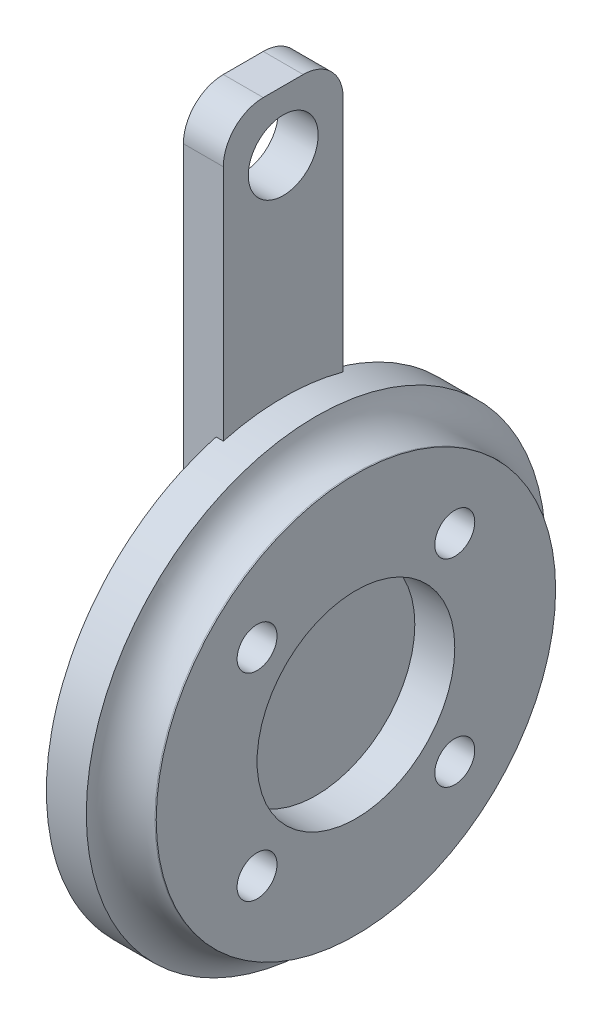
SolidWorks part; units mm, degrees
material "PLA"
ref_plane "Front Plane" through (0, 0, 0) normal (1, 0, 0) x (0, 1, 0)
ref_plane "Top Plane" through (0, 0, 0) normal (0, 0, 1) x (0, 1, 0)
ref_plane "Right Plane" through (0, 0, 0) normal (0, 1, 0) x (-1, 0, 0)
sketch "Sketch1" plane through (0, 0, 0) normal (1, 0, 0) x (0, 1, 0)
  circle A0 centre (0, 0) radius 11.5
  circle A1 centre (0, 0) radius 10.5
  dimension "D1" = 1
  dimension "D2" = 21
extrude "Boss-Extrude1" add sketch "Sketch1" along normal blind 2
extrude "Boss-Extrude2" add sketch "Sketch1<2>" along normal up to surface (2 mm away) contours A1 region at (0, 0, 0) up to face at (2, 0, -11.5)
sketch "Sketch1<2>" plane through (0, 0, 0) normal (1, 0, 0) x (0, 1, 0) same geometry as "Sketch1"
ref_plane "Plane1" through (-1.64, 0, 0) normal (-1, 0, 0) x (0, 0, 1)
sketch "Sketch2" plane through (-1.64, 0, 0) normal (-1, 0, 0) x (0, 0, 1)
  line L1 (-3, -5) -> (3, -5)
  line L2 (-3, -5) -> (-3, 5)
  line L3 (-3, 5) -> (3, 5)
  line L4 (3, -5) -> (3, 5)
  line L5 (0, 5) -> (0, -5) construction
  line L6 (-3, 0) -> (3, 0) construction
  point P0 (0, 0)
  dimension "D1" = 6
  dimension "D2" = 10
sketch "Sketch3" plane through (0, 0, 0) normal (-1, 0, 0) x (0, -1, 0)
  circle A0 centre (0, 0) radius 11.5
  circle A1 centre (0, 0) radius 9.5
  circle A2 centre (0, 0) radius 11.5 construction
  dimension "D1" = 2
extrude "Cut-Extrude2" cut sketch "Sketch3" against normal blind 1.5 contours A1 region at (0, 0, 0)
sketch "Sketch4" plane through (0, 0, 0) normal (-1, 0, 0) x (0, -1, 0)
  circle A1 centre (0, 0) radius 11.5
  circle A2 centre (0, 0) radius 11.5
  dimension "D1" = 0
loft "Loft1" add profiles "Sketch4", "Sketch2" connector at (0, 0, 11.5) connector at (-1.64, -5, -3)
sketch "Sketch6" plane through (-1.64, 0, 0) normal (-1, 0, 0) x (0, -1, 0)
  line L0 (0, 0) -> (-22, 0) construction
  line L1 (5, 3) -> (-25, 3)
  line L2 (-25, 3) -> (-25, -3)
  line L3 (-25, -3) -> (5, -3)
  line L4 (5, -3) -> (5, 3)
  circle A1 centre (-22, 0) radius 1.75
  dimension "D2" = 3.5
  dimension "D1" = 22
  dimension "D3" = 3
extrude "Boss-Extrude3" add sketch "Sketch6" against normal blind 2
sketch "Sketch7" plane through (2, 0, 0) normal (1, 0, 0) x (0, 1, 0)
  line L0 (0, 25.0823) -> (0, -32.3177) construction
  line L1 (-4.95, 4.95) -> (4.95, 4.95) construction
  line L2 (15.5615, 0) -> (-15.5615, 0) construction
  line L3 (4.95, 4.95) -> (4.95, -4.95) construction
  line L4 (-4.95, 4.95) -> (-4.95, -4.95) construction
  line L5 (-4.95, -4.95) -> (4.95, -4.95) construction
  circle A0 centre (0, 0) radius 10
  circle A1 centre (-4.95, 4.95) radius 1
  circle A2 centre (4.95, 4.95) radius 1
  circle A3 centre (4.95, -4.95) radius 1
  circle A4 centre (-4.95, -4.95) radius 1
  circle A5 centre (0, 0) radius 4.95
  dimension "D1" = 20
  dimension "D2" = 2
  dimension "D3" = 9.9
extrude "Boss-Extrude4" add sketch "Sketch7" along normal blind 2
fillet "Fillet1" radius 2 1 edges at (2, 0, -10)
fillet "Fillet2" radius 2 2 edges at (-0.64, 25, 3) (-0.64, 25, -3)
